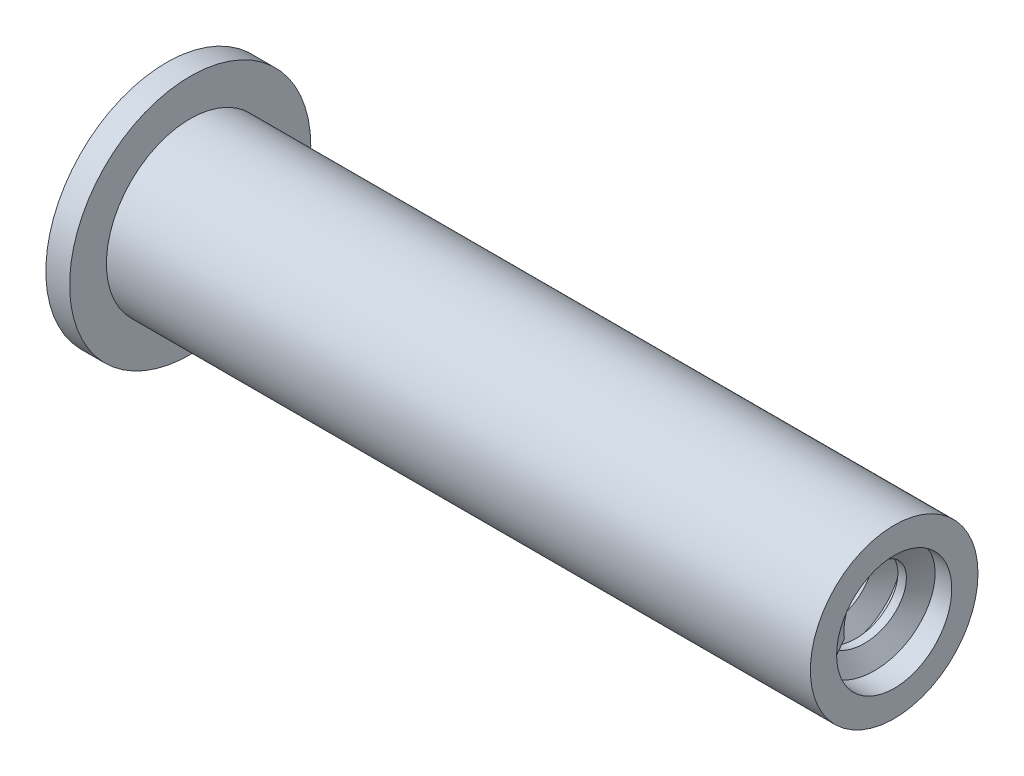
SolidWorks part; units mm, degrees
material "Plain Carbon Steel"
ref_plane "Front Plane" through (0, 0, 0) normal (0, 0, 1) x (1, 0, 0)
ref_plane "Top Plane" through (0, 0, 0) normal (0, 1, 0) x (1, 0, 0)
ref_plane "Right Plane" through (0, 0, 0) normal (1, 0, 0) x (0, 0, -1)
sketch "Sketch1" plane through (0, 0, 0) normal (0, 0, 1) x (1, 0, 0)
  line L0 (0, 0) -> (17.0942, 0)
  line L1 (17.0942, 0) -> (17.0942, 1.9685)
  line L2 (17.0942, 1.9685) -> (0.5588, 1.9685)
  line L3 (0.5588, 1.9685) -> (0.5588, 2.8321)
  line L4 (0.5588, 2.8321) -> (0, 2.8321)
  line L5 (0, 2.8321) -> (0, 0)
  line L6 (0, 0) -> (-7.6462, 0) construction
  dimension "D1" = 17.0942
  dimension "D2" = 1.9685
  dimension "D3" = 2.8321
  dimension "D4" = 0.5588
revolve "Revolve1" add sketch "Sketch1" angle 360 about L6
sketch "Sketch2" plane through (0, 0, 0) normal (-1, 0, 0) x (0, 0, 1)
  line L0 (0, 0) -> (0, 2.8321) construction
  line L1 (0, 1.778) -> (0.4106, 0.7112)
  line L2 (0, 0) -> (2.4527, 1.416) construction
  line L4 (0.4106, 0.7112) -> (1.5398, 0.889)
  line L20 (1.5398, 0.889) -> (0, 0)
  line L21 (0, 0) -> (0, 1.778)
  line L22 (0, 0) -> (2.7569, 0) construction
  circle A0 centre (0, 0) radius 2.8321 construction
  dimension "D1" = 3.556
  dimension "D2" = 60
  dimension "D3" = 0.889
  dimension "D4" = 1.0668
extrude "Cut-Extrude1" cut sketch "Sketch2" against normal blind 0.762
sketch "Sketch8" plane through (0, 0, 0) normal (0, 0, 1) x (1, 0, 0)
  line L0 (0, 0) -> (17.0942, 0) construction
  line L1 (17.0942, -1.9685) -> (17.0942, 1.9685) construction
pattern_circular "CirPattern1" count 6 over 360 about axis through (0, 0, 0) along (1, 0, 0) of "Cut-Extrude1"
hole_wizard "#6-32 Tapped Hole1" positions "Sketch3" profile "Sketch4" tap size "#6-32" standard "ANSI Inch"
sketch "Sketch3" plane through (17.0942, 0, 0) normal (1, 0, 0) x (0, 0, -1)
  point P0 (0, 0)
sketch "Sketch4" plane through (17.0942, 0, 0) normal (0, 1, 0) x (0, 0, -1)
  line L0 (0, 0) -> (0, 10.2107)
  line L1 (0, 10.2107) -> (1.3525, 9.398)
  line L2 (1.3525, 9.398) -> (1.3525, 0)
  line L5 (1.3525, 0) -> (0, 0)
  line L10 (0, 10.2107) -> (-1.3526, 9.398) construction
  line L11 (0, -6.35) -> (0, 107.95) construction
  dimension "Tap Drill Dia." = 2.7051
  dimension "Tap Drill Depth" = 9.398
  dimension "Drill Angle" = 118
thread "Thread1" pitch 0.7937 method extrude profile "Thread Profile1" start angle 0, offset 0, length 10, pitch 0.7937, diameter 2.7051
ref_plane "Plane1" through (17.0942, 0, 1.3525) normal (0, -1, 0) x (0, 0, 1)
sketch "Thread Profile1" plane through (17.0942, 0, 1.3525) normal (0, -1, 0) x (0, 0, 1)
  line L0 (0, 0) -> (0, 0.7937) construction
  line L11 (0, 0) -> (0, 0.6945)
  line L12 (0, 0.6945) -> (-0.4296, 0.4465)
  line L13 (-0.4296, 0.4465) -> (-0.4296, 0.248)
  line L15 (-0.4296, 0.248) -> (0, 0)
  line L17 (-0.4296, 0.3473) -> (0, 0.3473) construction
  point P2 (0, 0)
  dimension "Pitch" = 0.7937
  dimension "Profile_Angle" = 60
  dimension "Profile_Land" = 0.1984
  dimension "Profile_Height" = 0.4296
